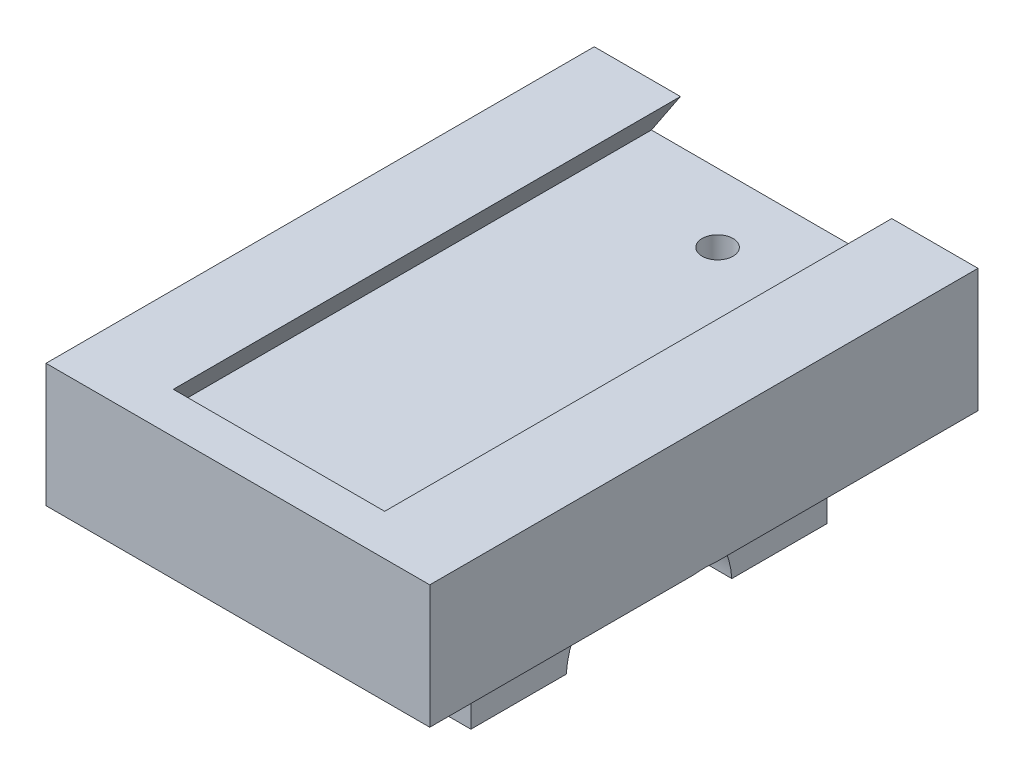
SolidWorks part; units mm, degrees
ref_plane "Front Plane" through (0, 0, 0) normal (0, 0, 1) x (1, 0, 0)
ref_plane "Top Plane" through (0, 0, 0) normal (0, 1, 0) x (1, 0, 0)
ref_plane "Right Plane" through (0, 0, 0) normal (1, 0, 0) x (0, 0, -1)
sketch "Sketch1" plane through (0, 0, 0) normal (0, 0, 1) x (1, 0, 0)
  line L0 (-28, 0) -> (28, 0)
  line L1 (28, 0) -> (28, 18)
  line L2 (28, 18) -> (-28, 18)
  line L3 (-28, 18) -> (-28, 0)
extrude "Channel Block" add sketch "Sketch1" along normal mid plane 80
sketch "Sketch2" plane through (0, 0, 0) normal (1, 0, 0) x (0, 0, -1)
  line L0 (-26, -11.25) -> (26, -11.25)
  line L1 (26, -11.25) -> (26, 0.5)
  line L2 (26, 0.5) -> (-26, 0.5)
  line L3 (-26, 0.5) -> (-26, -11.25)
extrude "Clamp Upper Half" add sketch "Sketch2" along normal mid plane 40
sketch "Sketch3" plane through (0, 0, 0) normal (0, 0, 1) x (1, 0, 0)
  line L0 (-15.0873, 18.5) -> (15.0873, 18.5)
  line L1 (15.0873, 18.5) -> (19.654, 11.65)
  line L2 (19.654, 11.65) -> (-19.654, 11.65)
  line L3 (-19.654, 11.65) -> (-15.0873, 18.5)
extrude "Dovetail Channel" cut sketch "Sketch3" against normal blind 41 and the other way blind 34
sketch "Sketch4" plane through (0, 0, 0) normal (1, 0, 0) x (0, 0, -1)
  circle A0 centre (0, -12) radius 12.1
extrude "Handlebar Bore" cut sketch "Sketch4" against normal through all and the other way through all
sketch "Sketch5" plane through (0, 0, 0) normal (0, 1, 0) x (1, 0, 0)
  circle A0 centre (0, -18.5) radius 3.2
  circle A1 centre (0, 18.5) radius 3.2
extrude "M5 Insert Holes" cut sketch "Sketch5" against normal blind 11.25
sketch "Sketch6" plane through (0, 0, 0) normal (0, 1, 0) x (1, 0, 0)
  circle A0 centre (0, 30) radius 2.25
extrude "Lock Clearance Hole" cut sketch "Sketch6" against normal through all and the other way through all
sketch "Sketch7" plane through (0, 0, 0) normal (0, 1, 0) x (1, 0, 0)
  circle A0 centre (0, 30) radius 2.8
extrude "Lock Insert Hole" cut sketch "Sketch7" along normal blind 8
equation "\"BrW\" = 56.0"
equation "\"BrL\" = 80.0"
equation "\"BrH\" = 18.0"
equation "\"RailW\" = 30.0"
equation "\"RailW2\" = 38.0"
equation "\"RailH\" = 6.0"
equation "\"Slide\" = 0.3"
equation "\"StopT\" = 6.0"
equation "\"TubeD\" = 22.2"
equation "\"Liner\" = 1.0"
equation "\"ClampW\" = 40.0"
equation "\"ClampZ\" = 26.0"
equation "\"ClampY\" = -12.0"
equation "\"CapT\" = 17.0"
equation "\"Gap\" = 0.75"
equation "\"BoltZ\" = 18.5"
equation "\"InsertD\" = 6.4"
equation "\"InsertL\" = 10.0"
equation "\"BoltD\" = 5.5"
equation "\"LockZ\" = -30.0"
equation "\"LockInsD\" = 5.6"
equation "\"LockInsL\" = 8.0"
equation "\"LockClear\" = 4.5"
equation "\"DovOff\" = 0.35"
